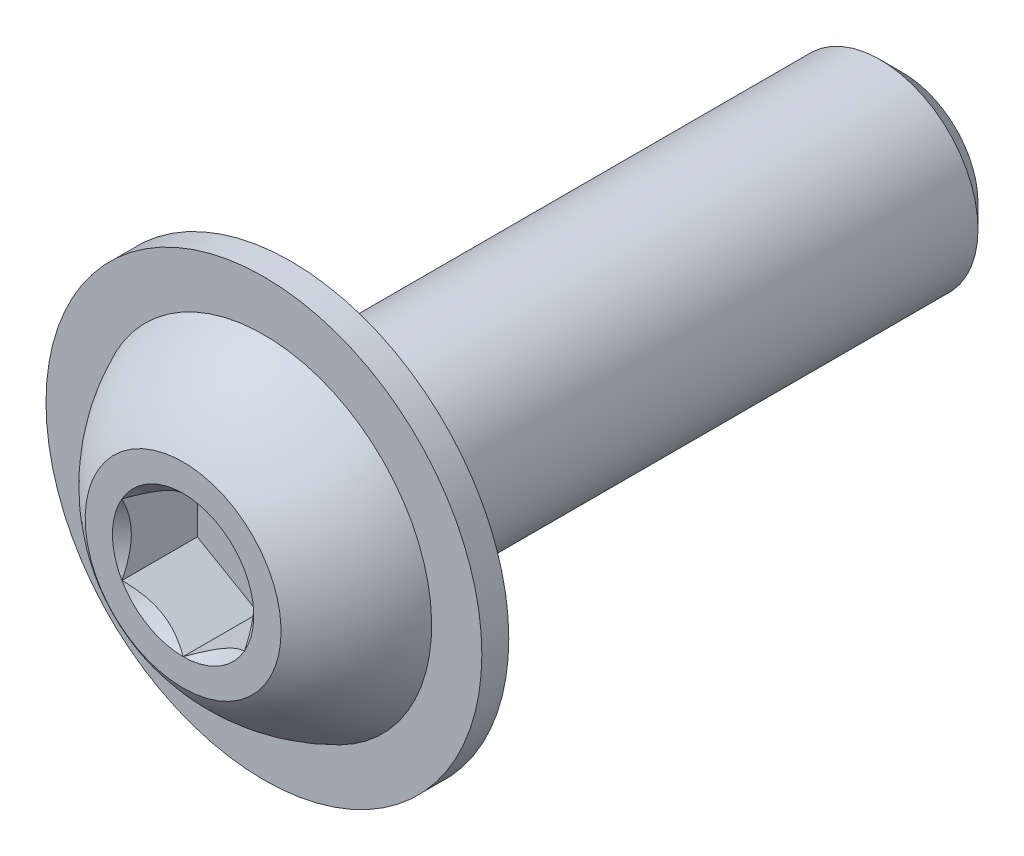
SolidWorks part; units mm, degrees
material "Alloy Steel"
ref_plane "Front" through (0, 0, 0) normal (0, 0, 1) x (1, 0, 0)
ref_plane "Top" through (0, 0, 0) normal (0, 1, 0) x (1, 0, 0)
ref_plane "Right" through (0, 0, 0) normal (1, 0, 0) x (0, 0, -1)
sketch "Sketch1" plane through (0, 0, 0) normal (1, 0, 0) x (0, 0, -1)
  line L2 (-10.3, 4) -> (14.7, 4)
  line L3 (14.7, 4) -> (14.7, 0)
  line L4 (14.7, -4) -> (13.45, -4) construction
  line L6 (-11.4, 6.85) -> (-10.3, 6.85) construction
  line L7 (14.7, 4) -> (14.7, -4) construction
  line L8 (-14.7, 0) -> (14.7, 0) construction
  line L9 (-10.3, 6.85) -> (-10.3, -6.85) construction
  line L11 (-10.3, 4) -> (-10.3, 0)
  line L13 (-14.7, 2.5) -> (-14.7, -2.5) construction
  line L14 (-14.7, 2.5) -> (-14.7, 4) construction
  line L15 (-11.4, 6.85) -> (-11.4, 8.9) construction
  line L16 (-11.4, 8.9) -> (-10.3, 8.9) construction
  line L17 (-10.3, 8.9) -> (-10.3, 6.85) construction
  line L18 (-10.3, 8.9) -> (-10.3, -8.9) construction
  arc A3 (-14.7, 4) -> (-11.4, 6.85) centre (-8.3648, 0) cw construction
  point P16 (10.325, -4)
  point P24 (0, 0)
  dimension "Thread OD" = 8
  dimension "D1" = 1.1
  dimension "Head Height" = 4.4
  dimension "Head Diameter" = 13.7
  dimension "Length" = 25
  dimension "Drive Size" = 5
  dimension "Flange Diameter" = 17.8
  dimension "D2" = 4.375
  dimension "Thread Pitch" = 1.25
sketch "Sketch13" plane through (0, 0, 0) normal (1, 0, 0) x (0, 0, -1)
  line L1 (-10.3, 4) -> (14.7, 4)
  line L2 (-10.3, 4) -> (-10.3, 0)
  line L3 (-10.3, 0) -> (14.7, 0)
  line L4 (14.7, 4) -> (14.7, 0)
revolve "Revolve1" add sketch "Sketch13" angle 360 about L8
chamfer "Chamfer1" distance 0.9375 angle 45 1 edges at (4, 0, -14.7)
sketch "Sketch7" plane through (0, 0, 0) normal (1, 0, 0) x (0, 0, -1)
  line L0 (-10.3, 6.85) -> (-10.3, -6.85) construction
  line L1 (-10.3, 6.85) -> (-10.3, 0)
  line L2 (-11.4, 6.85) -> (-11.4, 8.9)
  line L3 (-11.4, 8.9) -> (-10.3, 8.9)
  line L4 (-10.3, 8.9) -> (-10.3, 6.85)
  line L6 (-11.4, 6.85) -> (-10.3, 6.85) construction
  line L8 (-14.7, 0) -> (14.7, 0) construction
  line L12 (-11.4, 6.85) -> (-10.3, 6.85) construction
  line L13 (-14.7, 0) -> (-10.3, 0)
  line L14 (-14.7, 2.5) -> (-14.7, -2.5) construction
  line L16 (-14.7, 4) -> (-14.7, 0)
  arc A2 (-11.4, 6.85) -> (-14.7, 4) centre (-8.3648, 0) ccw construction
  arc A3 (-11.4, 6.85) -> (-14.7, 4) centre (-8.3648, 0) ccw
revolve "Revolve2" add sketch "Sketch7" angle 360 mid plane about L13
sketch "Sketch5" plane through (0, 0, 14.7) normal (0, 0, 1) x (1, 0, 0)
  line L1 (2.5, -1.4434) -> (2.5, 1.4434)
  line L2 (2.5, 1.4434) -> (0, 2.8868)
  line L3 (0, 2.8868) -> (-2.5, 1.4434)
  line L4 (-2.5, 1.4434) -> (-2.5, -1.4434)
  line L5 (-2.5, -1.4434) -> (0, -2.8868)
  line L6 (0, -2.8868) -> (2.5, -1.4434)
  circle A0 centre (0, 0) radius 2.5 construction
extrude "Cut-Extrude2" cut sketch "Sketch5" against normal blind 3.08
sketch "Sketch6" plane through (0, 0, 14.7) normal (0, 0, 1) x (1, 0, 0)
  circle A0 centre (0, 0) radius 2.8868
extrude "Cut-Extrude3" cut sketch "Sketch6" against normal blind 3.08 draft 45
split "Split1" [suppressed] bodies to split 113
sketch "Sketch14" [suppressed] plane through (0, 0, -10.2) normal (0, 0, -1) x (-1, 0, 0)
  circle A0 centre (0, 0) radius 4 construction
  circle A1 centre (0, 0) radius 4
curve "Helix/Spiral1" [suppressed]
sketch "Sketch16" [suppressed] plane through (0, 0, 0) normal (1, 0, 0) x (0, 0, -1)
  line L0 (11.3719, 4.1353) -> (10.1219, 4.1353) construction
  line L1 (10.1219, 4.1353) -> (10.7469, 3.0528) construction
  line L2 (10.7469, 3.0528) -> (11.3719, 4.1353) construction
  line L3 (11.2937, 4) -> (10.2, 4) construction
  line L4 (10.7469, 4.1353) -> (10.7469, 4) construction
  line L5 (11.3328, 4.0677) -> (10.1609, 4.0677) construction
  line L6 (10.825, 3.1881) -> (10.6687, 3.1881) construction
  line L7 (10.7469, 3.1881) -> (10.7469, 3.0528) construction
  line L8 (10.6687, 3.1881) -> (10.1609, 4.0677)
  line L9 (10.1609, 4.0677) -> (11.3328, 4.0677)
  line L10 (11.3328, 4.0677) -> (10.825, 3.1881)
  line L11 (10.825, 3.1881) -> (10.6687, 3.1881)
  point P11 (10.7469, 4.0677)
  dimension "D1" = 1.25
  dimension "D2" = 0.1562
sweep "Cut-Sweep1" [suppressed] cut profiles "Sketch16" path "Helix/Spiral1"
sketch "Sketch17" [suppressed] plane through (0, 0, 5.8) normal (0, 0, -1) x (-1, 0, 0)
  circle A1 centre (0, 0) radius 4
  circle A2 centre (0, 0) radius 4
  dimension "D1" = 0
extrude "Boss-Extrude1" [suppressed] add sketch "Sketch17" along normal up to next draft 20
equation "\"D3@Helix/Spiral1\" = \"Length@Sketch1\" + \"D4@Helix/Spiral1\""
equation "\"D1@Chamfer1\" = \"D4@Helix/Spiral1\" * .75"
equation "\"D1@Cut-Extrude2\" = \"Head Height@Sketch1\" * .7"
equation "\"D1@Sketch1\" = \"Head Height@Sketch1\" * .25"
equation "\"D1@Cut-Extrude3\" = \"D1@Cut-Extrude2\""
equation "\"D2@Sketch1\"=\"D4@Helix/Spiral1\"*3.5"
equation "\"D4@Helix/Spiral1\"=\"Thread Pitch@Sketch1\""
equation "\"D1@Sketch16\"=\"Thread Pitch@Sketch1\""
equation "\"D2@Sketch16\"=\"D1@Sketch16\"/8"
